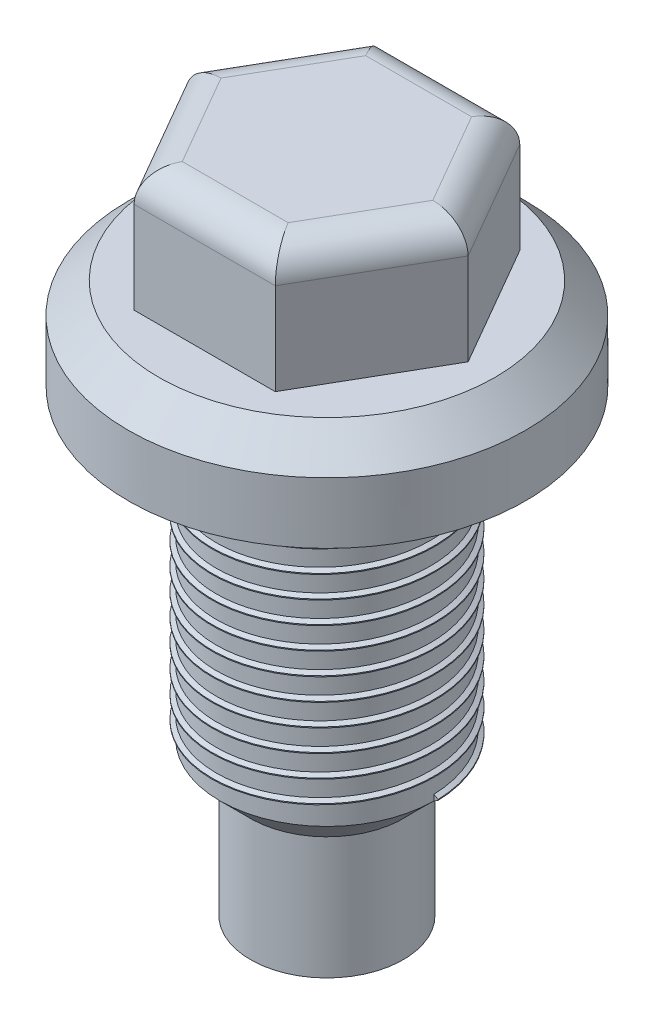
SolidWorks part; units mm, degrees
ref_plane "Front Plane" through (0, 0, 0) normal (0, 0, 1) x (1, 0, 0)
ref_plane "Top Plane" through (0, 0, 0) normal (0, 1, 0) x (1, 0, 0)
ref_plane "Right Plane" through (0, 0, 0) normal (1, 0, 0) x (0, 0, -1)
sketch "Sketch1" plane through (0, 0, 0) normal (0, 0, 1) x (1, 0, 0)
  line L0 (0, 0) -> (2.5, 0)
  line L1 (2.5, 0) -> (2.5, 5)
  line L2 (2.5, 5) -> (3.5, 5)
  line L3 (3.5, 5) -> (3.5, 15)
  line L4 (3.5, 15) -> (6.5, 15)
  line L5 (6.5, 15) -> (6.5, 18)
  line L6 (6.5, 18) -> (0, 18)
  line L7 (0, 18) -> (0, 0)
  dimension "D1" = 2.5
  dimension "D2" = 3.5
  dimension "D3" = 6.5
  dimension "D4" = 5
  dimension "D5" = 10
  dimension "D6" = 18
revolve "Revolve1" add sketch "Sketch1" angle 360 about L7
chamfer "Chamfer2" distance 1 angle 45 1 edges at (-2.5, 5, 0)
thread "Thread2" pitch 0.25 method extrude profile "Thread Profile2" start angle 0, offset 0, length 8, pitch 0.725, diameter 7
ref_plane "Plane2" through (3.5, 5, 0) normal (0, 0, 1) x (1, 0, 0)
sketch "Thread Profile2" plane through (3.5, 5, 0) normal (0, 0, 1) x (1, 0, 0)
  line L0 (0, 0) -> (0, 0.25) construction
  line L1 (0, 0) -> (0.1353, 0.0781)
  line L2 (0.1353, 0.0781) -> (0.1353, 0.1094)
  line L3 (0.1353, 0.1094) -> (0, 0.1875)
  line L4 (0.1353, 0.0937) -> (0, 0.0937) construction
  line L11 (0, 0) -> (0, 0.1875)
  point P2 (0, 0)
  dimension "Pitch" = 0.25
  dimension "Profile_Angle" = 60
  dimension "Profile_Land" = 0.0312
  dimension "Profile_Height" = 0.1353
chamfer "Chamfer3" distance 1 angle 45 1 edges at (-6.5, 18, 0)
sketch "Sketch11" plane through (0, 18, 0) normal (0, 1, 0) x (1, 0, 0)
  line L1 (2.3094, -4) -> (4.6188, 0)
  line L2 (4.6188, 0) -> (2.3094, 4)
  line L3 (2.3094, 4) -> (-2.3094, 4)
  line L4 (-2.3094, 4) -> (-4.6188, 0)
  line L5 (-4.6188, 0) -> (-2.3094, -4)
  line L6 (-2.3094, -4) -> (2.3094, -4)
  circle A0 centre (0, 0) radius 4 construction
  point P1 (0, 0)
  dimension "D1" = 8
extrude "Boss-Extrude1" add sketch "Sketch11" along normal blind 4
chamfer "Chamfer4" [suppressed] distance 1 angle 45
fillet "Fillet2" radius 1 6 edges at (-3.4641, 22, -2) (0, 22, -4) (3.4641, 22, -2) (3.4641, 22, 2) (0, 22, 4) (-3.4641, 22, 2)
